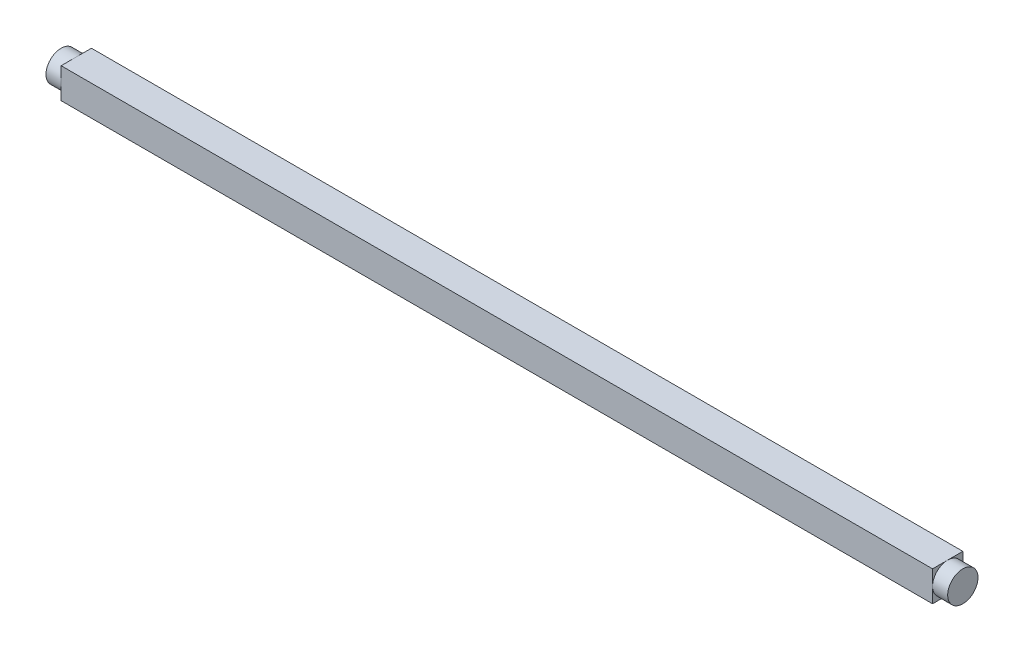
SolidWorks part; units mm, degrees
ref_plane "Front Plane" through (0, 0, 0) normal (0, 0, 1) x (1, 0, 0)
ref_plane "Top Plane" through (0, 0, 0) normal (0, 1, 0) x (1, 0, 0)
ref_plane "Right Plane" through (0, 0, 0) normal (1, 0, 0) x (0, 0, -1)
sketch "Sketch1" plane through (0, 0, 0) normal (1, 0, 0) x (0, 0, -1)
  line L1 (3.175, -3.175) -> (-3.175, -3.175)
  line L2 (3.175, -3.175) -> (3.175, 3.175)
  line L3 (3.175, 3.175) -> (-3.175, 3.175)
  line L4 (-3.175, -3.175) -> (-3.175, 3.175)
  line L5 (3.175, -3.175) -> (-3.175, 3.175) construction
  line L6 (3.175, 3.175) -> (-3.175, -3.175) construction
  point P0 (0, 0)
  dimension "D1" = 6.35
extrude "Boss-Extrude1" add sketch "Sketch1" along normal blind 94.4562
sketch "Sketch2" plane through (94.4562, 0, 0) normal (1, 0, 0) x (0, 0, -1)
  line L0 (3.175, 3.175) -> (-3.175, 3.175) construction
  line L2 (3.9688, -3.9688) -> (-3.9688, -3.9688)
  line L3 (3.9688, -3.9688) -> (3.9688, 3.9688)
  line L4 (3.9688, 3.9688) -> (-3.9688, 3.9687)
  line L5 (-3.9688, -3.9688) -> (-3.9688, 3.9687)
  line L6 (3.9688, -3.9688) -> (-3.9688, 3.9687) construction
  line L7 (3.9688, 3.9688) -> (-3.9688, -3.9688) construction
  circle A0 centre (0, 0) radius 3.175
  dimension "D1" = 7.9375
extrude "Cut-Extrude1" cut sketch "Sketch2" against normal blind 3.175
mirror "Mirror1" about plane through (0, 0, 0) normal (1, 0, 0) of bodies 102
